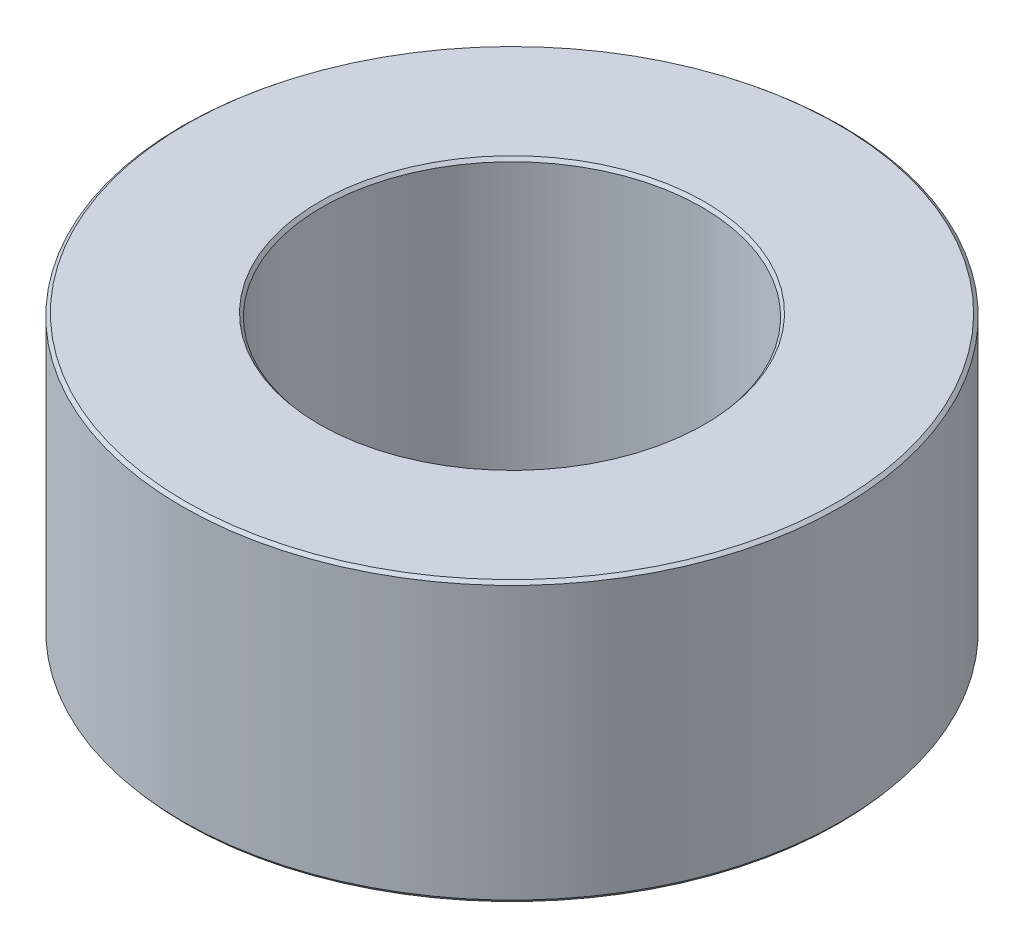
SolidWorks part; units mm, degrees
ref_plane "Front Plane" through (0, 0, 0) normal (0, 0, 1) x (1, 0, 0)
ref_plane "Top Plane" through (0, 0, 0) normal (0, 1, 0) x (1, 0, 0)
ref_plane "Right Plane" through (0, 0, 0) normal (1, 0, 0) x (0, 0, -1)
sketch "Sketch1" plane through (0, 0, 0) normal (0, 1, 0) x (1, 0, 0)
  circle A0 centre (0, 0) radius 37.5
  dimension "SLEEVE_OD" = 75
extrude "Boss-Extrude1" add sketch "Sketch1" along normal blind 31.6752
sketch "Sketch2" plane through (0, 0, 0) normal (0, 1, 0) x (1, 0, 0)
  circle A0 centre (0, 0) radius 21.6078
  dimension "BORE_D" = 43.2157
extrude "Cut-Extrude1" cut sketch "Sketch2" along normal through all
chamfer "Chamfer1" distance 0.3132 angle 49.843 4 edges at (0, 31.6752, 21.6078) (0, 0, 21.6078) (0, 0, 37.5) (0, 31.6752, 37.5) first distance on face at (0, 31.6752, 21.6078) first distance on face at (0, 0, 21.6078) first distance on face at (0, 31.6752, 37.5)
